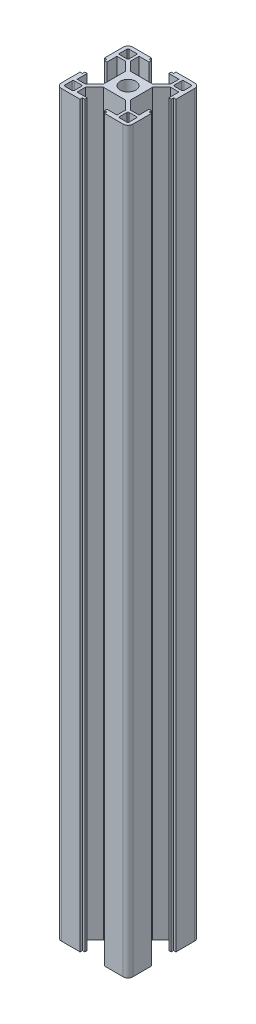
SolidWorks part; units mm, degrees
material "6061 Alloy"
ref_plane "Front Plane" through (0, 0, 0) normal (0, 0, 1) x (1, 0, 0)
ref_plane "Top Plane" through (0, 0, 0) normal (0, 1, 0) x (1, 0, 0)
ref_plane "Right Plane" through (0, 0, 0) normal (1, 0, 0) x (0, 0, -1)
sketch "Sketch1" plane through (0, 0, 0) normal (0, 1, 0) x (1, 0, 0)
  line L0 (-8.375, 13) -> (-4.125, 13)
  line L1 (-13, 15) -> (-4.125, 15)
  line L2 (-15, 13) -> (-15, 4.125)
  line L3 (-13, -15) -> (-4.125, -15)
  line L4 (15, 13) -> (15, 4.125)
  line L5 (-15, 15) -> (15, -15) construction
  line L6 (-15, -15) -> (15, 15) construction
  line L7 (-11.5, 11.5) -> (11.5, 11.5) construction
  line L8 (-11.5, 11.5) -> (-11.5, -11.5) construction
  line L9 (-11.5, -11.5) -> (11.5, -11.5) construction
  line L10 (11.5, 11.5) -> (11.5, -11.5) construction
  line L11 (-11.5, 11.5) -> (11.5, -11.5) construction
  line L12 (-11.5, -11.5) -> (11.5, 11.5) construction
  line L13 (-13.5, 13.5) -> (-9.5, 13.5)
  line L14 (-13.5, 13.5) -> (-13.5, 9.5)
  line L15 (-13.5, 9.5) -> (-9.5, 9.5)
  line L16 (-9.5, 13.5) -> (-9.5, 9.5)
  line L17 (-13.5, 13.5) -> (-9.5, 9.5) construction
  line L18 (-13.5, 9.5) -> (-9.5, 13.5) construction
  line L19 (13.5, 13.5) -> (9.5, 13.5)
  line L20 (13.5, 13.5) -> (13.5, 9.5)
  line L21 (13.5, 9.5) -> (9.5, 9.5)
  line L22 (9.5, 13.5) -> (9.5, 9.5)
  line L23 (13.5, 13.5) -> (9.5, 9.5) construction
  line L24 (13.5, 9.5) -> (9.5, 13.5) construction
  line L25 (13.5, -13.5) -> (9.5, -13.5)
  line L26 (13.5, -13.5) -> (13.5, -9.5)
  line L27 (13.5, -9.5) -> (9.5, -9.5)
  line L28 (9.5, -13.5) -> (9.5, -9.5)
  line L29 (13.5, -13.5) -> (9.5, -9.5) construction
  line L30 (13.5, -9.5) -> (9.5, -13.5) construction
  line L31 (-13.5, -13.5) -> (-9.5, -13.5)
  line L32 (-13.5, -13.5) -> (-13.5, -9.5)
  line L33 (-13.5, -9.5) -> (-9.5, -9.5)
  line L34 (-9.5, -13.5) -> (-9.5, -9.5)
  line L35 (-13.5, -13.5) -> (-9.5, -9.5) construction
  line L36 (-13.5, -9.5) -> (-9.5, -13.5) construction
  line L37 (0, 15) -> (0, 13) construction
  line L38 (-4.125, 15) -> (-4.125, 13)
  line L39 (4.125, 15) -> (4.125, 13)
  line L40 (4.125, 15) -> (13, 15)
  line L41 (-15, 15) -> (15, 15) construction
  line L42 (4.125, 13) -> (8.375, 13)
  line L43 (-15, 13) -> (15, 13) construction
  line L44 (8.375, 9.5064) -> (4.6186, 5.75)
  line L45 (-4.6186, -5.75) -> (4.6186, -5.75)
  line L46 (-8.375, 13) -> (-8.375, 9.5)
  line L47 (8.375, 13) -> (8.375, 9.5)
  line L48 (-8.375, 15) -> (-8.375, 13) construction
  line L49 (8.375, 15) -> (8.375, 13) construction
  line L50 (-5.75, -4.6186) -> (-5.75, 4.6186)
  line L51 (-4.6186, 5.75) -> (4.6186, 5.75)
  line L52 (5.75, -4.6186) -> (5.75, 4.6186)
  line L53 (-5.75, -5.75) -> (5.75, 5.75) construction
  line L54 (-5.75, 5.75) -> (5.75, -5.75) construction
  line L55 (-8.375, 9.5064) -> (-4.6186, 5.75)
  line L56 (-10.6314, 9.5) -> (-5.75, 4.6186)
  line L57 (-14.4343, 15.5657) -> (15.5657, -14.4343) construction
  line L58 (15, 4.125) -> (13, 4.125)
  line L59 (13, 8.375) -> (13, 4.125)
  line L60 (13, 8.375) -> (9.5, 8.375)
  line L61 (9.5064, 8.375) -> (5.75, 4.6186)
  line L62 (9.5064, -8.375) -> (5.75, -4.6186)
  line L63 (13, -8.375) -> (9.5, -8.375)
  line L64 (13, -4.125) -> (13, -8.375)
  line L65 (15, -4.125) -> (13, -4.125)
  line L66 (4.125, -15) -> (4.125, -13)
  line L67 (8.375, -13) -> (4.125, -13)
  line L68 (8.375, -13) -> (8.375, -9.5)
  line L69 (8.375, -9.5064) -> (4.6186, -5.75)
  line L70 (-8.375, -9.5064) -> (-4.6186, -5.75)
  line L71 (-8.375, -13) -> (-8.375, -9.5)
  line L72 (-4.125, -13) -> (-8.375, -13)
  line L73 (-4.125, -15) -> (-4.125, -13)
  line L74 (-15, -4.125) -> (-13, -4.125)
  line L75 (-13, -8.375) -> (-13, -4.125)
  line L76 (-13, -8.375) -> (-9.5, -8.375)
  line L77 (-9.5064, -8.375) -> (-5.75, -4.6186)
  line L78 (-9.5064, 8.375) -> (-5.75, 4.6186)
  line L79 (-13, 8.375) -> (-9.5, 8.375)
  line L80 (-13, 4.125) -> (-13, 8.375)
  line L81 (-15, 4.125) -> (-13, 4.125)
  line L82 (-15, -4.125) -> (-15, -13)
  line L83 (4.125, -15) -> (13, -15)
  line L84 (15, -4.125) -> (15, -13)
  circle A0 centre (0, 0) radius 3.25
  circle A1 centre (0, 0) radius 3.25
  circle A2 centre (0, 0) radius 3.25
  circle A3 centre (0, 0) radius 3.25
  arc A4 (-15, -13) -> (-13, -15) centre (-13, -13) ccw
  arc A5 (13, -15) -> (15, -13) centre (13, -13) ccw
  arc A6 (13, 15) -> (15, 13) centre (13, 13) cw
  arc A7 (-13, 15) -> (-15, 13) centre (-13, 13) ccw
  point P0 (0, 0)
  point P6 (0, 0)
  point P31 (0, 0)
  point P48 (-15.5657, 14.4343)
  point P49 (14.4343, -15.5657)
  point P60 (0, 5.75)
  point P102 (0, 0)
  dimension "D17" = 6.5
  dimension "D10" = 2
  dimension "D1" = 30
  dimension "D2" = 30
  dimension "D3" = 23
  dimension "D4" = 23
  dimension "D5" = 4
  dimension "D6" = 4
  dimension "D7" = 4
  dimension "D8" = 4
  dimension "D12" = 3.5
  dimension "D16" = 11.5
  dimension "D11" = 11.5
  dimension "D9" = 2
  dimension "D18" = 0.8
extrude "Boss-Extrude1" add sketch "Sketch1" along normal blind 310 contours L1 A7 L2 L81 L80 L79 L15 L14 L13 L16 L56 L50 L77 L76 L75 L74 L82 A4 L3 L73 L72 L71 L70 L45 L69 L68 L67 L66 L83 A5 L84 L65 L64 L63 L62 L52 L61 region at (-8.7993, 0, -11.2532)
sketch "Sketch2" plane through (0, 310, 0) normal (0, 1, 0) x (1, 0, 0)
  line L0 (15, 4.125) -> (14, 4.125)
  line L1 (-4.125, 15) -> (-5.125, 15)
  line L2 (-4.125, 15) -> (-4.125, 14)
  line L3 (-4.125, 14) -> (-5.125, 14)
  line L4 (-5.125, 15) -> (-5.125, 14)
  line L5 (4.125, 15) -> (5.125, 15)
  line L6 (4.125, 15) -> (4.125, 14)
  line L7 (4.125, 14) -> (5.125, 14)
  line L8 (5.125, 15) -> (5.125, 14)
  line L9 (15, 4.125) -> (15, 5.125)
  line L10 (15, 5.125) -> (14, 5.125)
  line L11 (14, 4.125) -> (14, 5.125)
  line L12 (15, -4.125) -> (14, -4.125)
  line L13 (15, -4.125) -> (15, -5.125)
  line L14 (15, -5.125) -> (14, -5.125)
  line L15 (14, -4.125) -> (14, -5.125)
  line L16 (4.125, -15) -> (4.125, -14)
  line L17 (4.125, -15) -> (5.125, -15)
  line L18 (5.125, -15) -> (5.125, -14)
  line L19 (4.125, -14) -> (5.125, -14)
  line L20 (-4.125, -15) -> (-4.125, -14)
  line L21 (-4.125, -15) -> (-5.125, -15)
  line L22 (-5.125, -15) -> (-5.125, -14)
  line L23 (-4.125, -14) -> (-5.125, -14)
  line L24 (-15, -4.125) -> (-14, -4.125)
  line L25 (-15, -4.125) -> (-15, -5.125)
  line L26 (-15, -5.125) -> (-14, -5.125)
  line L27 (-14, -4.125) -> (-14, -5.125)
  line L28 (-15, 4.125) -> (-14, 4.125)
  line L29 (-15, 4.125) -> (-15, 5.125)
  line L30 (-15, 5.125) -> (-14, 5.125)
  line L31 (-14, 4.125) -> (-14, 5.125)
  point P36 (0, 0)
  dimension "D1" = 1
  dimension "D2" = 1
  dimension "D3" = 1
  dimension "D4" = 1
  dimension "D5" = 4
extrude "Cut-Extrude1" cut sketch "Sketch2" against normal through all
fillet "Fillet1" radius 0.5 16 edges at (9.5, 155, 13.5) (-13.5, 155, 13.5) (-13.5, 155, -9.5) (9.5, 155, -9.5) (-13.5, 155, 9.5) (9.5, 155, 9.5) (9.5, 155, -13.5) (-13.5, 155, -13.5) (-9.5, 155, -13.5) (13.5, 155, -13.5) (13.5, 155, 9.5) (-9.5, 155, 9.5) (13.5, 155, 13.5) (-9.5, 155, 13.5) (-9.5, 155, -9.5) (13.5, 155, -9.5)
sketch "Sketch3" plane through (0, 0, -15) normal (0, 0, -1) x (-1, 0, 0)
  line L2 (-15, 310) -> (-15, 0) construction
  line L11 (-15, 51.9615) -> (-15, 0)
  line L12 (-15, 0) -> (15, 0)
  line L13 (15, 0) -> (-15, 51.9615)
  line L14 (-15, 155) -> (15, 155) construction
  line L15 (15, 310) -> (15, 0) construction
  line L27 (0, 284.0192) -> (0, 310)
  line L28 (0, 310) -> (15, 310)
  line L29 (15, 310) -> (0, 284.0192)
  line L30 (-5.125, 310) -> (-13, 310) construction
  line L31 (0, 284.0192) -> (-15, 292.6795)
  line L32 (-15, 292.6795) -> (-15, 310)
  line L33 (-15, 310) -> (0, 310)
  dimension "D1" = 30
  dimension "D2" = 60
  dimension "D3" = 30
  dimension "D4" = 90
extrude "Cut-Extrude2" [suppressed] cut sketch "Sketch3" against normal through all
equation "\"L\"= 385"
